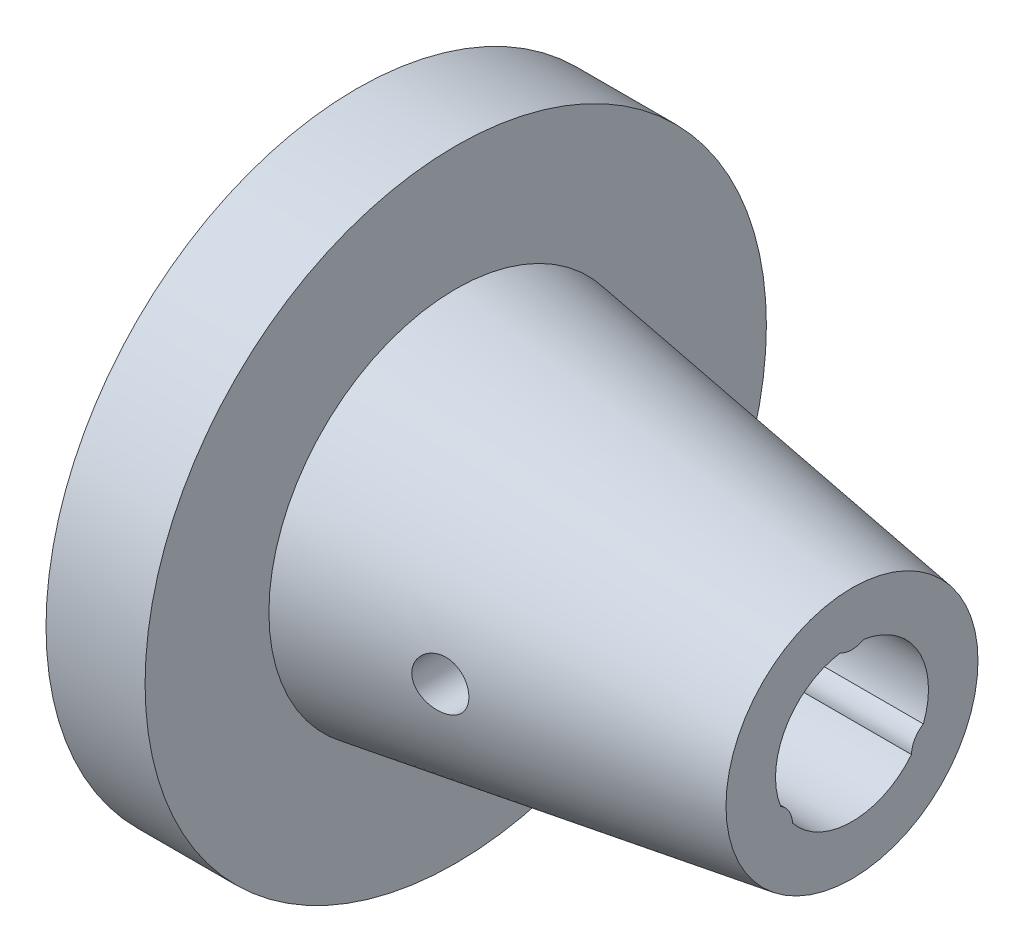
SolidWorks part; units mm, degrees
ref_plane "Front Plane" through (0, 0, 0) normal (0, 0, 1) x (1, 0, 0)
ref_plane "Top Plane" through (0, 0, 0) normal (0, 1, 0) x (1, 0, 0)
ref_plane "Right Plane" through (0, 0, 0) normal (1, 0, 0) x (0, 0, -1)
sketch "Sketch3" plane through (0, 0, 0) normal (0, 0, 1) x (1, 0, 0)
  line L0 (0, 9.9568) -> (0, 2.4511)
  line L1 (3.175, 5.9881) -> (3.175, 9.9568)
  line L2 (3.175, 9.9568) -> (0, 9.9568)
  line L3 (3.175, 5.9881) -> (15.875, 4.0386)
  line L4 (15.875, 4.0386) -> (15.875, 2.4511)
  line L5 (15.875, 2.4511) -> (0, 2.4511)
  line L6 (0, 0) -> (15.875, 0) construction
  dimension "D1" = 9.9568
  dimension "D2" = 12.7
  dimension "D3" = 1.5875
  dimension "D4" = 3.175
  dimension "D5" = 3.9688
  dimension "D6" = 2.4511
revolve "Revolve1" add sketch "Sketch3" angle 360 about L6
sketch "Sketch5" plane through (15.875, 0, 0) normal (-1, 0, 0) x (0, 0, 1)
  line L0 (0, 0) -> (0, 3.1802) construction
  arc A0 (-0.381, 2.4213) -> (0.381, 2.4213) centre (0, 0) cw
  circle A1 centre (0, 0) radius 2.4511 construction
  arc A2 (-0.381, 2.4213) -> (0.381, 2.4213) centre (0, 3.1194) ccw
  point P2 (0, 2.3241)
  point P11 (0, 2.4511)
  dimension "D1" = 0.127
  dimension "D2" = 0.762
extrude "Boss-Extrude2" add sketch "Sketch5" along normal blind 6.35
fillet "Fillet1" radius 0.254 1 edges at (9.525, 2.3241, 0)
ref_axis "Axis2" through (-0.7937, 0, 0) along (1, 0, 0)
pattern_circular "CirPattern3" count 3 over 360 about axis through (-0.7937, 0, 0) along (1, 0, 0) of "Fillet1", "Boss-Extrude2"
sketch "Sketch6" plane through (0, 0, 0) normal (0, 0, 1) x (1, 0, 0)
  line L0 (0, 0) -> (7.9375, 0) construction
  line L2 (15.875, -4.0386) -> (15.875, 4.0386) construction
  circle A0 centre (7.9375, 0) radius 0.7937
  dimension "D2" = 1.5875
  dimension "D1" = 7.9375
extrude "Cut-Extrude1" cut sketch "Sketch6" against normal through all and the other way through all
